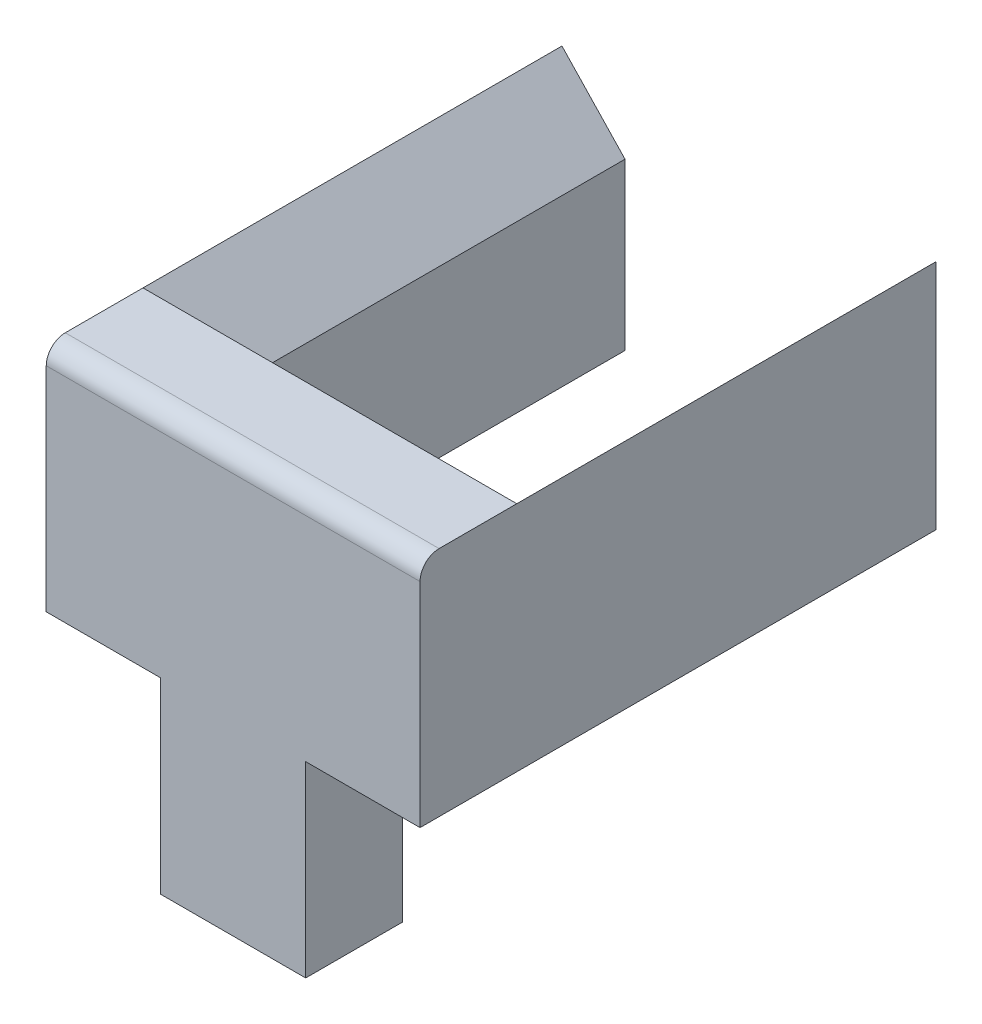
SolidWorks part; units mm, degrees
ref_plane "Front Plane" through (0, 0, 0) normal (0, 0, 1) x (1, 0, 0)
ref_plane "Top Plane" through (0, 0, 0) normal (0, 1, 0) x (1, 0, 0)
ref_plane "Right Plane" through (0, 0, 0) normal (1, 0, 0) x (0, 0, -1)
sketch "Sketch1" plane through (0, 0, 0) normal (0, 1, 0) x (1, 0, 0)
  line L0 (-13.9881, 12.8425) -> (-13.9881, -12.5575)
  line L1 (-13.9881, -12.5575) -> (24.1119, -12.5575)
  line L2 (24.1119, -12.5575) -> (24.1119, 12.8425)
  line L3 (24.1119, 12.8425) -> (-13.9881, 12.8425)
  line L4 (5.0619, 12.8425) -> (5.0619, -12.5575) construction
extrude "Boss-Extrude1" add sketch "Sketch1" along normal blind 110.1598 contours L3 L0 L1 L2
sketch "Sketch2" plane through (24.1119, 0, 0) normal (1, 0, 0) x (0, 0, -1)
  line L0 (-12.5575, 110.1598) -> (12.8425, 110.1598)
  line L1 (12.8425, 110.1598) -> (12.8425, 49.1998)
  line L2 (12.8425, 110.1598) -> (12.8425, 0) construction
  line L3 (12.8425, 49.1998) -> (-12.5575, 49.1998)
  line L4 (-12.5575, 110.1598) -> (-12.5575, 0) construction
  line L5 (-12.5575, 49.1998) -> (-12.5575, 110.1598)
extrude "Boss-Extrude2" add sketch "Sketch2" along normal blind 30.0228 contours L1 L3 L5 L0
sketch "Sketch3" plane through (-13.9881, 0, 0) normal (-1, 0, 0) x (0, 0, 1)
  line L0 (12.5575, 110.1598) -> (12.5575, 0) construction
  line L1 (-12.8425, 110.1598) -> (12.5575, 110.1598)
  line L2 (-12.8425, 110.1598) -> (-12.8425, 49.1998)
  line L3 (-12.8425, 49.1998) -> (12.5575, 49.1998)
  line L4 (12.5575, 110.1598) -> (12.5575, 49.1998)
extrude "Boss-Extrude3" add sketch "Sketch3" along normal blind 30.0228
sketch "Sketch4" plane through (0, 0, -12.8425) normal (0, 0, -1) x (-1, 0, 0)
  line L0 (-54.1347, 110.1598) -> (-54.1347, 49.1998)
  line L4 (-37.5767, 92.6998) -> (-54.1347, 110.1598)
  line L5 (-37.5767, 92.6998) -> (-37.5767, 49.1998)
  line L6 (-54.1347, 49.1998) -> (-24.1119, 49.1998) construction
  line L7 (-37.5767, 49.1998) -> (-54.1347, 49.1998)
  line L11 (44.0109, 110.1598) -> (44.0109, 49.1998)
  line L12 (44.0109, 49.1998) -> (27.4529, 49.1998)
  line L13 (27.4529, 49.1998) -> (27.4529, 92.6998)
  line L14 (44.0109, 49.1998) -> (13.9881, 49.1998) construction
  line L15 (27.4529, 92.6998) -> (44.0109, 110.1598)
extrude "Boss-Extrude4" add sketch "Sketch4" along normal blind 110.0074
sketch "Sketch8" plane through (0, 0, 0) normal (0, -1, 0) x (1, 0, 0)
  line L0 (5.0619, 12.5575) -> (5.0619, -12.8425) construction
  line L1 (-13.9881, 12.5575) -> (24.1119, 12.5575) construction
  line L2 (24.1119, -12.8425) -> (-13.9881, -12.8425) construction
  line L3 (5.0619, -0.1425) -> (15.0619, -0.1425) construction
  line L4 (5.0619, -0.1425) -> (-4.9381, -0.1425) construction
  line L5 (-9.9839, -0.1425) -> (-9.9839, 7.4775)
  line L6 (-9.9839, -0.1425) -> (-9.9839, -7.7828)
  line L8 (20.2653, -7.7828) -> (20.2653, 7.4775)
  line L9 (20.2653, 7.4775) -> (15.0619, 7.4775)
  line L10 (15.0619, 7.4775) -> (15.0619, 3.6675)
  line L11 (15.0619, 3.6675) -> (-4.9381, 3.6675)
  line L12 (-4.9381, 3.6675) -> (-4.9381, 7.4775)
  line L13 (-4.9381, 7.4775) -> (-9.9839, 7.4775)
  line L14 (-9.9839, -7.7828) -> (-4.9381, -7.7828)
  line L15 (-4.9381, -7.7828) -> (-4.9381, -3.9607)
  line L16 (-4.9381, -3.9607) -> (15.0619, -3.9607)
  line L17 (15.0619, -3.9607) -> (15.0619, -7.7828)
  line L18 (15.0619, -7.7828) -> (20.2653, -7.7828)
extrude "Cut-Extrude1" cut sketch "Sketch8" against normal blind 25.4
fillet "Fillet3" radius 5 1 edges at (5.0619, 110.1598, 12.5575) type face fillet first side face at (5.0619, 110.1598, -0.1425) second side face at (5.0619, 52.1399, 12.5575)
